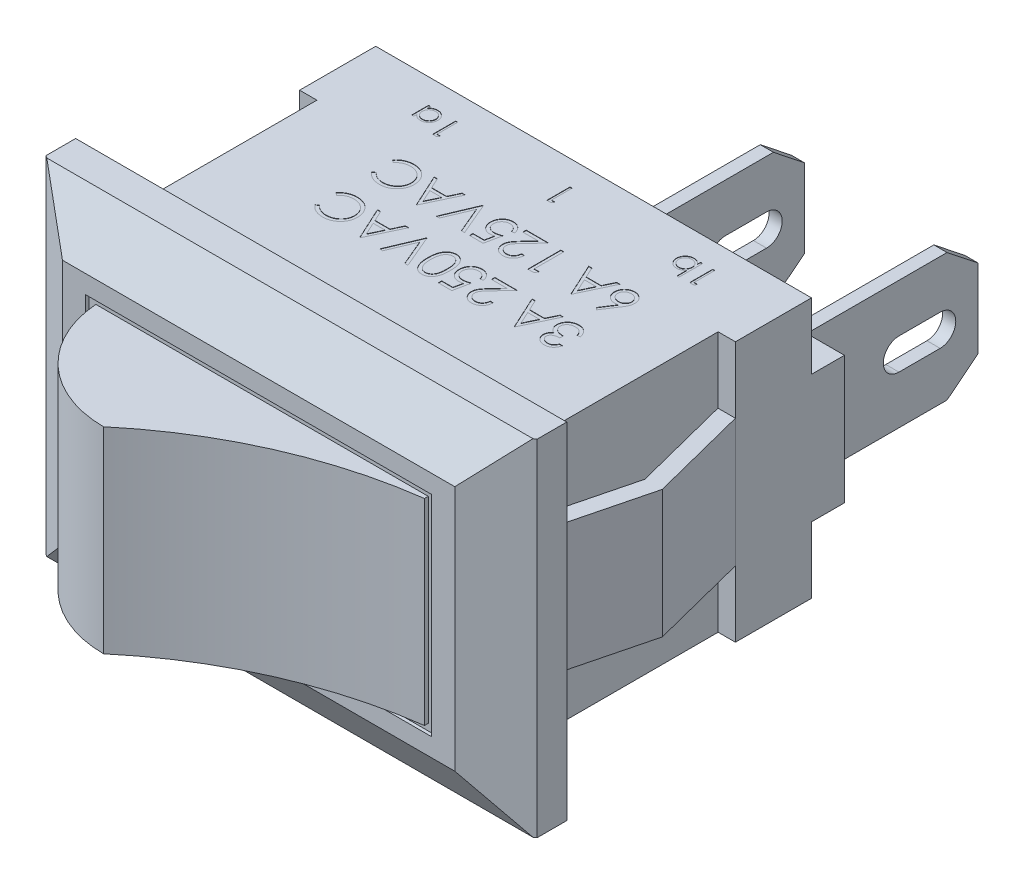
SolidWorks part; units mm, degrees
ref_plane "Front Plane" through (0, 0, 0) normal (0, 0, 1) x (1, 0, 0)
ref_plane "Top Plane" through (0, 0, 0) normal (0, 1, 0) x (1, 0, 0)
ref_plane "Right Plane" through (0, 0, 0) normal (1, 0, 0) x (0, 0, -1)
sketch "Sketch1" plane through (0, 0, 0) normal (0, 0, 1) x (1, 0, 0)
  line L1 (-7.455, 5.24) -> (7.455, 5.24)
  line L2 (-7.455, 5.24) -> (-7.455, -5.24)
  line L3 (-7.455, -5.24) -> (7.455, -5.24)
  line L4 (7.455, 5.24) -> (7.455, -5.24)
  dimension "D1" = 14.91
  dimension "D2" = 7.455
  dimension "D3" = 10.48
  dimension "D4" = 5.24
extrude "Boss-Extrude1" add sketch "Sketch1" against normal blind 1.9
sketch "Sketch2" plane through (0, -5.24, 0) normal (0, -1, 0) x (1, 0, 0)
  line L0 (-7.455, -1) -> (-5.955, 0)
  line L1 (-7.455, -1.9) -> (-7.455, 0) construction
  line L2 (-7.455, 0) -> (7.455, 0) construction
  line L3 (-5.955, 0) -> (-7.455, 0)
  line L4 (-7.455, 0) -> (-7.455, -1)
  line L5 (7.455, -1) -> (7.455, 0)
  line L6 (7.455, -1.9) -> (7.455, 0) construction
  line L7 (7.455, 0) -> (5.955, 0)
  line L8 (5.955, 0) -> (7.455, -1)
  dimension "D1" = 1.5
  dimension "D2" = 1.5
  dimension "D3" = 1
  dimension "D4" = 1
sketch "Sketch4" plane through (-7.455, 0, 0) normal (-1, 0, 0) x (0, 0, 1)
  line L0 (-0.95, -5.24) -> (0, -5.24)
  line L1 (-1.9, -5.24) -> (0, -5.24) construction
  line L2 (0, 5.24) -> (0, -5.24) construction
  line L3 (0, -5.24) -> (0, -3.74)
  line L4 (0, -3.74) -> (-0.95, -5.24)
  line L5 (-0.95, 5.24) -> (0, 3.74)
  line L6 (-1.9, 5.24) -> (0, 5.24) construction
  line L7 (0, 3.74) -> (0, 5.24)
  line L8 (0, 5.24) -> (-0.95, 5.24)
  dimension "D1" = 1.5
  dimension "D2" = 1.5
extrude "Cut-Extrude2" cut sketch "Sketch2" against normal through all
extrude "Cut-Extrude3" cut sketch "Sketch4" against normal through all
sketch "Sketch5" plane through (0, 0, 0) normal (0, 0, 1) x (1, 0, 0)
  line L1 (-5.25, 3.185) -> (5.25, 3.185)
  line L2 (-5.25, 3.185) -> (-5.25, -3.185)
  line L3 (-5.25, -3.185) -> (5.25, -3.185)
  line L4 (5.25, 3.185) -> (5.25, -3.185)
  line L5 (-5.05, 2.985) -> (5.05, 2.985)
  line L6 (-5.05, 2.985) -> (-5.05, -2.985)
  line L7 (-5.05, -2.985) -> (5.05, -2.985)
  line L8 (5.05, 2.985) -> (5.05, -2.985)
  dimension "D1" = 10.5
  dimension "D2" = 5.25
  dimension "D3" = 6.37
  dimension "D4" = 3.185
  dimension "D5" = 0.2
  dimension "D6" = 0.2
  dimension "D7" = 0.2
  dimension "D8" = 0.2
extrude "Cut-Extrude4" cut sketch "Sketch5" against normal blind 0.1
sketch "Sketch6" plane through (0, 0, -1.9) normal (0, 0, -1) x (-1, 0, 0)
  line L1 (-6.09, 3.95) -> (6.09, 3.95)
  line L2 (-6.09, 3.95) -> (-6.09, -3.95)
  line L3 (-6.09, -3.95) -> (6.09, -3.95)
  line L4 (6.09, 3.95) -> (6.09, -3.95)
  dimension "D1" = 12.18
  dimension "D2" = 6.09
  dimension "D3" = 7.9
  dimension "D4" = 3.95
extrude "Boss-Extrude2" add sketch "Sketch6" along normal blind 8.27
sketch "Sketch7" plane through (0, 3.95, 0) normal (0, 1, 0) x (1, 0, 0)
  line L1 (6.09, 10.17) -> (6.615, 10.17)
  line L2 (6.09, 10.17) -> (6.09, 7.86)
  line L3 (6.09, 7.86) -> (6.615, 7.86)
  line L4 (6.615, 10.17) -> (6.615, 7.86)
  line L5 (-6.09, 10.17) -> (-6.615, 10.17)
  line L6 (-6.09, 10.17) -> (-6.09, 7.86)
  line L7 (-6.09, 7.86) -> (-6.615, 7.86)
  line L8 (-6.615, 10.17) -> (-6.615, 7.86)
  dimension "D1" = 13.23
  dimension "D2" = 2.31
extrude "Boss-Extrude3" add sketch "Sketch7" against normal up to vertex (7.9 mm away) up to point (-6.09, -3.95, -10.17)
sketch "Sketch8" plane through (0, 0, 0) normal (0, 1, 0) x (1, 0, 0)
  line L0 (-6.615, 7.86) -> (-6.085, 7.86)
  line L1 (-6.085, 7.86) -> (-6.8453, 4.8806)
  line L2 (-6.8453, 4.8806) -> (-6.09, 1.9)
  line L3 (-6.09, 1.9) -> (-6.62, 1.9)
  line L4 (-6.62, 1.9) -> (-7.3753, 4.8806)
  line L5 (-7.3753, 4.8806) -> (-6.615, 7.86)
  dimension "D1" = 0.53
  dimension "D2" = 0.53
  dimension "D3" = 0
  dimension "D4" = 0
  dimension "D5" = 0
  dimension "D6" = 151.465
extrude "Boss-Extrude4" add sketch "Sketch8" along normal blind 1.94 and the other way blind 1.94
mirror "Mirror1" about plane through (0, 0, 0) normal (1, 0, 0) of "Boss-Extrude4"
sketch "Sketch9" plane through (0, 0, -10.17) normal (0, 0, -1) x (-1, 0, 0)
  line L0 (-6.615, -1.94) -> (-6.615, 1.94) construction
  line L1 (-6.615, 1.94) -> (-5.465, 1.94)
  line L2 (-6.615, 1.94) -> (-6.615, -1.94)
  line L3 (-6.615, -1.94) -> (-5.465, -1.94)
  line L4 (-3.915, 1.94) -> (-3.915, -1.94)
  line L5 (6.615, -3.95) -> (6.615, 3.95) construction
  line L6 (-1.35, 1.94) -> (-0.2, 1.94)
  line L7 (-1.35, 1.94) -> (-1.35, -1.94)
  line L8 (-1.35, -1.94) -> (-0.2, -1.94)
  line L9 (1.35, 1.94) -> (1.35, -1.94)
  line L10 (6.615, 1.94) -> (5.465, 1.94)
  line L11 (6.615, 1.94) -> (6.615, -1.94)
  line L12 (6.615, -1.94) -> (5.465, -1.94)
  line L13 (3.915, 1.94) -> (3.915, -1.94)
  line L14 (-6.615, -3.95) -> (-6.615, 3.95) construction
  line L15 (-5.065, 1.94) -> (-3.915, 1.94)
  line L17 (-5.465, 1.94) -> (-5.465, -1.94)
  line L19 (-5.065, 1.94) -> (-5.065, -1.94)
  line L21 (-0.2, 1.94) -> (-0.2, -1.94)
  line L23 (0.2, 1.94) -> (0.2, -1.94)
  line L25 (5.065, 1.94) -> (5.065, -1.94)
  line L27 (5.465, 1.94) -> (5.465, -1.94)
  line L28 (0.2, 1.94) -> (1.35, 1.94)
  line L29 (5.065, 1.94) -> (3.915, 1.94)
  line L30 (5.065, -1.94) -> (3.915, -1.94)
  line L31 (0.2, -1.94) -> (1.35, -1.94)
  line L32 (-5.065, -1.94) -> (-3.915, -1.94)
  dimension "D1" = 2.7
  dimension "D2" = 1.35
  dimension "D3" = 0.4
  dimension "D4" = 1.15
  dimension "D5" = 1.15
  dimension "D6" = 0.4
  dimension "D7" = 0.4
  dimension "D8" = 1.15
  dimension "D9" = 2.565
  dimension "D10" = 1.15
extrude "Boss-Extrude5" add sketch "Sketch9" along normal blind 1
sketch "Sketch10" plane through (0, 0, 0) normal (1, 0, 0) x (0, 0, -1)
  line L0 (10.17, 1.94) -> (15.4293, 1.94)
  line L1 (15.4293, 1.94) -> (16.37, 1.195)
  line L2 (16.37, 1.195) -> (16.37, -1.195)
  line L3 (16.37, -1.195) -> (15.4293, -1.94)
  line L4 (15.4293, -1.94) -> (10.17, -1.94)
  line L5 (10.17, -1.94) -> (10.17, 1.94)
  line L6 (13.97, 0) -> (15.22, 0) construction
  line L7 (13.97, 0.475) -> (15.22, 0.475)
  line L8 (13.97, -0.475) -> (15.22, -0.475)
  arc A0 (13.97, 0.475) -> (13.97, -0.475) centre (13.97, 0) ccw
  arc A1 (15.22, -0.475) -> (15.22, 0.475) centre (15.22, 0) ccw
  point P2 (14.595, 0)
  dimension "D1" = 2.39
  dimension "D2" = 1.2
  dimension "D3" = 1.2
  dimension "D4" = 3.88
  dimension "D5" = 0.745
  dimension "D6" = 6.2
  dimension "D7" = 1.195
  dimension "D8" = 1.25
  dimension "D9" = 1.15
  dimension "D10" = 0.95
extrude "Boss-Extrude6" add sketch "Sketch10" along normal blind 0.2 and the other way blind 0.2
ref_plane "Plane1" through (2.635, 0, 0) normal (1, 0, 0) x (0, 0, -1)
mirror "Mirror2" about plane through (2.635, 0, 0) normal (1, 0, 0) of "Boss-Extrude6"
sketch "Sketch11" plane through (0, 3.95, 0) normal (0, 1, 0) x (1, 0, 0)
  line L0 (4.17, 5.9) -> (-3.28, 5.9) construction
  line L1 (4.17, 7.62) -> (-3.28, 7.62) construction
  line L2 (6.09, 7.86) -> (6.09, 1.9) construction
  line L3 (-6.09, 1.9) -> (6.09, 1.9) construction
  line L4 (4.67, 9.42) -> (3.27, 9.42) construction
  line L5 (0.77, 9.42) -> (-0.63, 9.42) construction
  line L6 (-3.13, 9.42) -> (-4.53, 9.42) construction
  line L7 (6.615, 7.86) -> (6.615, 10.17) construction
  text T0 "3A 250VAC" font "Century Gothic" height 1
  text T1 "6A 125VAC" font "Century Gothic" height 1
  text T2 "1b" font "Century Gothic" height 0.7
  text T3 "1" font "Century Gothic" height 0.7
  text T4 "1a" font "Century Gothic" height 0.7
  dimension "D1" = 1.92
  dimension "D2" = 7.45
  dimension "D3" = 1.72
  dimension "D4" = 4
  dimension "D5" = 1.4
  dimension "D6" = 1.4
  dimension "D7" = 1.4
  dimension "D8" = 2.5
  dimension "D9" = 2.5
  dimension "D10" = 1.8
  dimension "D11" = 1.945
extrude "Cut-Extrude5" cut sketch "Sketch11" against normal blind 0.01
sketch "Sketch12" plane through (0, -3.95, 0) normal (0, -1, 0) x (1, 0, 0)
  line L0 (-4.79, -3.2) -> (-1.29, -3.2) construction
  line L1 (-4.79, -5.7) -> (-0.79, -5.7) construction
  line L2 (-4.665, -9.25) -> (-3.265, -9.25) construction
  line L3 (-0.765, -9.25) -> (0.635, -9.25) construction
  line L4 (3.135, -9.25) -> (4.535, -9.25) construction
  line L5 (-6.615, -10.17) -> (-6.615, -7.86) construction
  line L6 (-7.455, -1.9) -> (7.455, -1.9) construction
  line L7 (-6.09, -7.86) -> (-6.09, -1.9) construction
  text T0 "KCD1" font "Century Gothic" height 1
  text T1 "CE" font "Century Gothic" height 1
  text T2 "2a" font "Century Gothic" height 0.7
  text T3 "2" font "Century Gothic" height 0.7
  text T4 "2b" font "Century Gothic" height 0.7
  dimension "D1" = 1.4
  dimension "D2" = 1.4
  dimension "D3" = 1.4
  dimension "D4" = 1.95
  dimension "D5" = 2.5
  dimension "D6" = 2.5
  dimension "D7" = 3.5
  dimension "D8" = 1.3
  dimension "D9" = 1.3
  dimension "D10" = 4
  dimension "D11" = 3.8
  dimension "D12" = 1.3
  dimension "D13" = 3.55
extrude "Cut-Extrude6" cut sketch "Sketch12" against normal blind 0.01
sketch "Sketch13" plane through (0, 0, 0) normal (0, 0, 1) x (1, 0, 0)
  line L0 (5.05, 2.985) -> (-5.05, 2.985) construction
  line L1 (5.05, -2.985) -> (5.05, 2.985) construction
  line L2 (-5.05, -2.985) -> (5.05, -2.985) construction
  line L3 (-5.05, 2.985) -> (-5.05, -2.985) construction
  line L4 (5.05, 2.985) -> (-5.05, 2.985)
  line L5 (5.05, -2.985) -> (5.05, 2.985)
  line L6 (-5.05, -2.985) -> (5.05, -2.985)
  line L7 (-5.05, 2.985) -> (-5.05, -2.985)
extrude "Boss-Extrude7" add sketch "Sketch13" along normal blind 3
sketch "Sketch16" plane through (0, 2.985, 0) normal (0, 1, 0) x (1, 0, 0)
  line L0 (-5.05, 0.1) -> (-5.05, -3) construction
  line L1 (5.05, -3) -> (-5.05, -3) construction
  line L2 (5.05, 0.1) -> (-5.05, 0.1) construction
  line L3 (5.05, 0.1) -> (5.05, -3) construction
  line L6 (-5.05, 0.1) -> (-5.05, -3)
  line L7 (5.05, -3) -> (-1.7071, -3)
  line L8 (5.05, -0.0148) -> (5.05, -3)
  arc A0 (5.05, -0.0148) -> (-1.7071, -3) centre (6.7863, -13.0852) ccw
  arc A1 (0.9855, -1.2446) -> (-1.8623, -3) centre (-1.8623, 0.1877) ccw
extrude "Cut-Extrude9" cut sketch "Sketch16" against normal blind 8 contours L7 A0 L8
sketch "Sketch17" plane through (0, 2.985, 0) normal (0, 1, 0) x (1, 0, 0)
  line L0 (-5.05, 0.1) -> (-5.05, -3) construction
  line L1 (-1.7071, -3) -> (-5.05, -3) construction
  line L4 (-5.05, 0.1) -> (-5.05, -3)
  line L5 (-1.7071, -3) -> (-5.05, -3)
  line L8 (-5.0412, 0.1005) -> (-5.05, 0.1)
  arc A0 (-5.0412, 0.1005) -> (-1.7071, -3) centre (-1.7071, 0.3429) ccw
extrude "Cut-Extrude10" cut sketch "Sketch17" against normal blind 8
